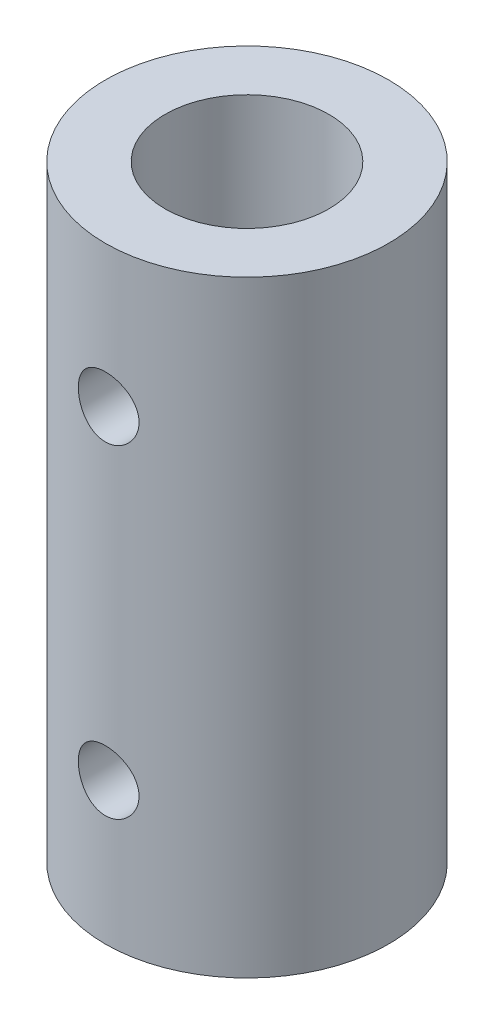
SolidWorks part; units mm, degrees
ref_plane "Front Plane" through (0, 0, 0) normal (0, 0, 1) x (1, 0, 0)
ref_plane "Top Plane" through (0, 0, 0) normal (0, 1, 0) x (1, 0, 0)
ref_plane "Right Plane" through (0, 0, 0) normal (1, 0, 0) x (0, 0, -1)
sketch "Sketch1" plane through (0, 0, 0) normal (0, 1, 0) x (1, 0, 0)
  circle A0 centre (0, 0) radius 7
  circle A1 centre (0, 0) radius 4.05
  circle A2 centre (0, 0) radius 1.7
  dimension "D1" = 8.1
  dimension "D2" = 14
  dimension "D3" = 3.4
extrude "Boss-Extrude1" add sketch "Sketch1" along normal blind 15 contours A0 A1 region at (-6.802, 0, 0)
extrude "Boss-Extrude2" add sketch "Sketch1<3>" against normal blind 15 contours A0 A1 | A1 A2 region at (-6.802, 0, 0) region at (-3.9354, 0, 0)
sketch "Sketch1<3>" plane through (0, 0, 0) normal (0, 1, 0) x (1, 0, 0) same geometry as "Sketch1"
sketch "Sketch2" plane through (0, 0, 0) normal (0, 0, 1) x (1, 0, 0)
  line L0 (-7, -15) -> (7, -15) construction
  line L1 (4.05, 15) -> (-4.05, 15) construction
  circle A0 centre (0, 8) radius 1.5
  circle A1 centre (0, -8) radius 1.5
  dimension "D1" = 3
  dimension "D2" = 3
  dimension "D3" = 7
  dimension "D4" = 7
extrude "Cut-Extrude1" cut sketch "Sketch2" against normal through all both and the other way through all
